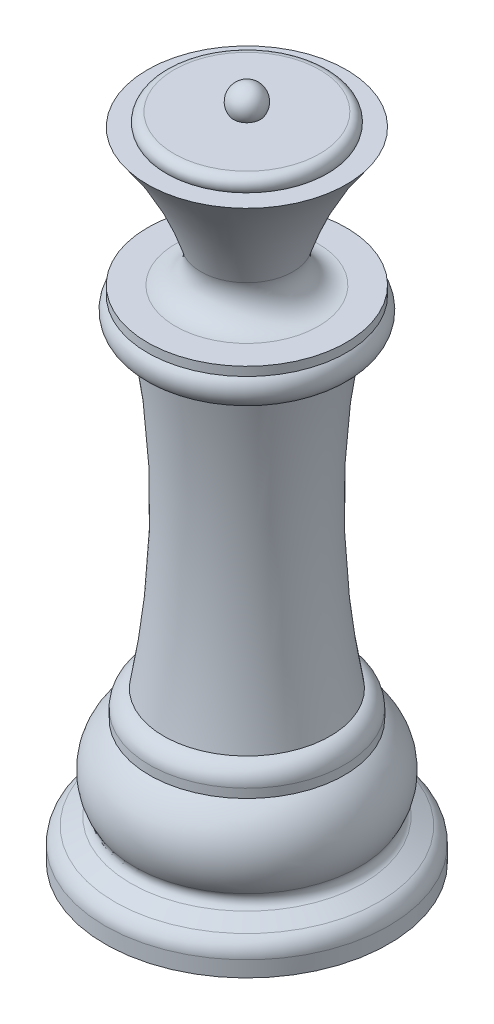
SolidWorks part; units mm, degrees
ref_plane "Front Plane" through (0, 0, 0) normal (0, 0, 1) x (1, 0, 0)
ref_plane "Top Plane" through (0, 0, 0) normal (0, 1, 0) x (1, 0, 0)
ref_plane "Right Plane" through (0, 0, 0) normal (1, 0, 0) x (0, 0, -1)
sketch "Sketch1" plane through (0, 0, 0) normal (0, 0, 1) x (1, 0, 0)
  line L10 (-0.0214, -10) -> (13.9594, -10)
  line L12 (11.992, -5) -> (15.9594, -7)
  line L13 (15.9594, -7) -> (15.9594, -10)
  line L14 (15.9594, -10) -> (13.9594, -10)
  line L15 (10.9594, 3.97) -> (10.9594, 4.97)
  line L16 (11.1823, 46.29) -> (11.1823, 45.29)
  line L17 (-0.0214, 65.9982) -> (-0.0214, -10)
  line L18 (11.1823, 61.7) -> (9.0483, 61.7)
  line L20 (8.1823, 63.2) -> (1.5, 63.2)
  line L21 (11.1823, 46.29) -> (4.1823, 46.29)
  arc A10 (10.9594, 3.97) -> (11.992, -5) centre (7.5515, -0.9667) cw
  arc A11 (9.3458, 6.97) -> (10.9594, 4.97) centre (8.9598, 5.0076) cw
  arc A12 (11.1823, 45.29) -> (9.1823, 41.97) centre (9.7588, 43.8851) cw
  arc A13 (9.3458, 6.97) -> (9.1823, 41.97) centre (107.7198, 24.9299) cw
  arc A15 (9.0483, 61.7) -> (8.1823, 63.2) centre (8.1823, 62.2) ccw
  arc A16 (1.5, 63.2) -> (-0.0214, 65.9982) centre (-0.0214, 64.1855) ccw
  arc A17 (11.1823, 61.7) -> (4.1823, 46.29) centre (39.762, 39.4228) ccw
  point P15 (0.6823, 60.57)
  dimension "D3" = 8.97
  dimension "D9" = 2
  dimension "D12" = 100
  dimension "D11" = 35
  dimension "D8" = 2
  dimension "D15" = 1
  dimension "D16" = 1.5
  dimension "D17" = 75.9982
  dimension "D10" = 5.9988
  dimension "D1" = 3
  dimension "D2" = 2
  dimension "D4" = 1
  dimension "D5" = 2
  dimension "D6" = 3.32
  dimension "D7" = 1
  dimension "D13" = 15.41
revolve "Revolve1" add sketch "Sketch1" angle 360 about L17 region at (5.001, 23.0132, 0)
fillet "Fillet1" radius 2 1 edges at (-16.0022, -7, 0)
fillet "Fillet2" radius 1 1 edges at (-12.0347, -5, 0)
fillet "Fillet3" radius 3 1 edges at (-4.225, 46.29, 0)
